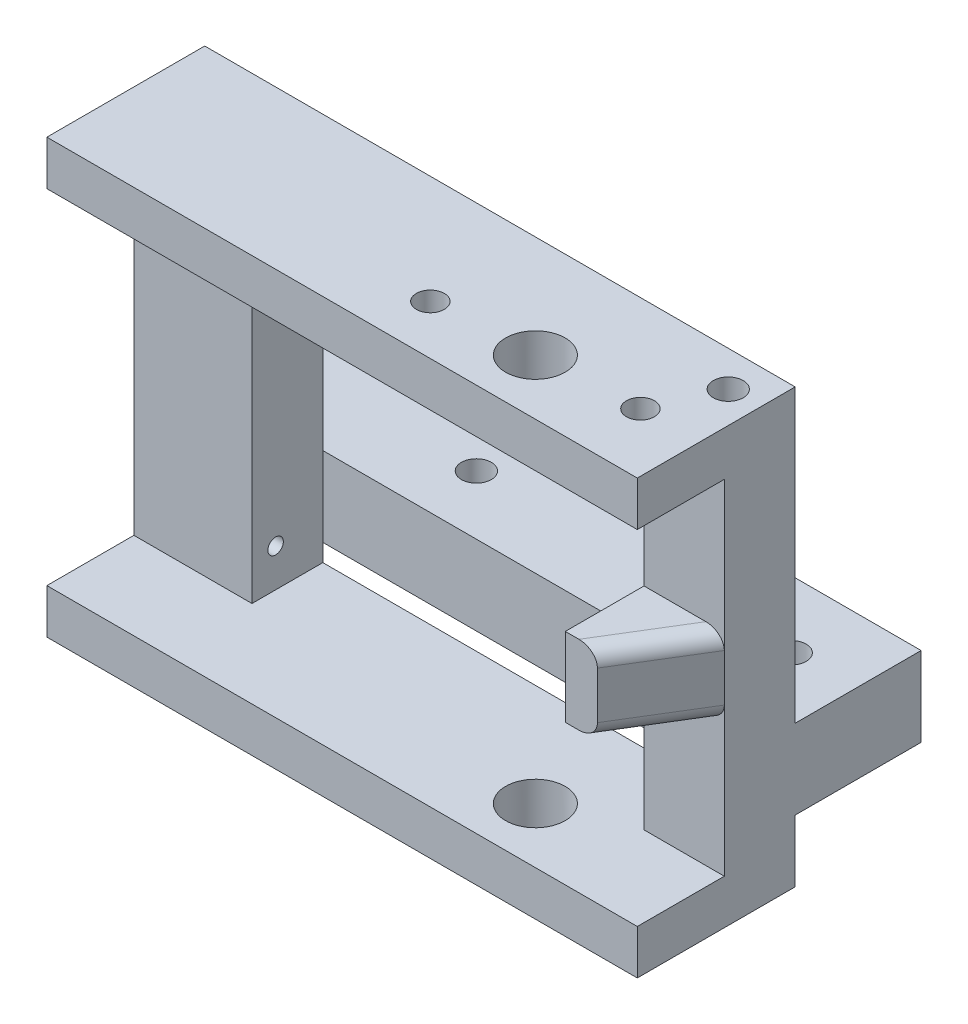
SolidWorks part; units mm, degrees
ref_plane "Front Plane" through (0, 0, 0) normal (0, 0, 1) x (1, 0, 0)
ref_plane "Top Plane" through (0, 0, 0) normal (0, 1, 0) x (1, 0, 0)
ref_plane "Right Plane" through (0, 0, 0) normal (1, 0, 0) x (0, 0, -1)
sketch "Sketch1" plane through (0, 0, 0) normal (0, 0, 1) x (1, 0, 0)
  line L1 (57.15, -34.925) -> (-57.15, -34.925)
  line L2 (57.15, -34.925) -> (57.15, 34.925)
  line L3 (57.15, 34.925) -> (-57.15, 34.925)
  line L4 (-57.15, -34.925) -> (-57.15, 34.925)
  line L5 (57.15, -34.925) -> (-57.15, 34.925) construction
  line L6 (57.15, 34.925) -> (-57.15, -34.925) construction
  point P0 (0, 0)
  dimension "D1" = 69.85
  dimension "D2" = 114.3
extrude "Boss-Extrude1" add sketch "Sketch1" along normal blind 57.15
sketch "Sketch2" plane through (0, 0, 57.15) normal (0, 0, 1) x (1, 0, 0)
  line L0 (-57.15, 34.925) -> (-57.15, -34.925) construction
  line L1 (57.15, -27.725) -> (-57.15, -27.725)
  line L2 (57.15, -27.725) -> (57.15, 27.725)
  line L3 (57.15, 27.725) -> (-57.15, 27.725)
  line L4 (-57.15, -27.725) -> (-57.15, 27.725)
  line L5 (57.15, -27.725) -> (-57.15, 27.725) construction
  line L6 (57.15, 27.725) -> (-57.15, -27.725) construction
  line L7 (57.15, 34.925) -> (-57.15, 34.925) construction
  point P0 (0, 0)
  dimension "D1" = 7.2
extrude "Cut-Extrude2" cut sketch "Sketch2" against normal blind 25.4
sketch "Sketch3" plane through (0, 0, 0) normal (0, 0, -1) x (-1, 0, 0)
  line L0 (-57.15, -34.925) -> (-57.15, 34.925) construction
  line L1 (57.15, 34.925) -> (-57.15, 34.925)
  line L2 (57.15, 34.925) -> (57.15, -12.065)
  line L3 (57.15, -12.065) -> (-57.15, -12.065)
  line L4 (-57.15, 34.925) -> (-57.15, -12.065)
  dimension "D1" = 46.99
extrude "Cut-Extrude3" cut sketch "Sketch3" against normal blind 20.32
sketch "Sketch5" plane through (0, -34.925, 0) normal (0, -1, 0) x (1, 0, 0)
  line L0 (-3.81, 10.79) -> (46.99, 10.79) construction
  line L1 (57.15, 20.32) -> (-57.15, 20.32) construction
  line L2 (57.15, 57.15) -> (57.15, 0) construction
  circle A0 centre (-3.81, 10.79) radius 2.415
  circle A1 centre (46.99, 10.79) radius 2.415
  dimension "D3" = 4.83
  dimension "D4" = 10.16
  dimension "D1" = 9.53
  dimension "D2" = 50.8
sketch "Sketch7" plane through (0, -34.925, 0) normal (0, -1, 0) x (1, 0, 0)
  line L0 (57.15, 57.15) -> (57.15, 0) construction
  line L2 (-57.15, 31.75) -> (57.15, 31.75) construction
  circle A0 centre (31.75, 36.83) radius 4.8
  dimension "D1" = 9.6
  dimension "D2" = 25.4
  dimension "D3" = 5.08
extrude "Cut-Extrude6" cut sketch "Sketch7" against normal up to surface (69.85 mm away) up to face at (0, 34.925, 38.735)
sketch "Sketch8" plane through (0, 34.925, 0) normal (0, 1, 0) x (1, 0, 0)
  line L0 (15.7798, -37.8068) -> (47.7202, -35.8532) construction
  line L1 (57.15, -31.75) -> (-57.15, -31.75) construction
  circle A0 centre (31.75, -36.83) radius 16 construction
  circle A1 centre (15.7798, -37.8068) radius 2.25
  circle A2 centre (47.7202, -35.8532) radius 2.25
  dimension "D1" = 32
  dimension "D2" = 4.5
  dimension "D3" = 3.5
sketch "Sketch9" plane through (0, 0, 31.75) normal (0, 0, 1) x (1, 0, 0)
  line L0 (57.15, 34.925) -> (-57.15, 34.925) construction
  line L5 (57.15, 27.725) -> (-57.15, 27.725) construction
  line L6 (-19.05, 27.725) -> (44.196, 27.725)
  line L7 (-19.05, 27.725) -> (-19.05, -27.725)
  line L8 (-19.05, -27.725) -> (44.196, -27.725)
  line L9 (44.196, 27.725) -> (44.196, -27.725)
  line L10 (-57.15, -27.725) -> (57.15, -27.725) construction
  line L11 (-57.15, 27.725) -> (-57.15, -27.725) construction
  line L12 (57.15, -27.725) -> (57.15, 27.725) construction
  line L13 (-57.15, -34.925) -> (-38.1, -34.925)
  line L14 (-57.15, -34.925) -> (-57.15, 34.925)
  line L15 (-57.15, 34.925) -> (-38.1, 34.925)
  line L16 (-38.1, -34.925) -> (-38.1, 34.925)
  line L17 (-57.15, -34.925) -> (-38.1, 34.925) construction
  line L18 (-57.15, 34.925) -> (-38.1, -34.925) construction
  line L19 (-57.15, -34.925) -> (57.15, -34.925) construction
  point P5 (-47.625, 0)
  dimension "D1" = 12.954
  dimension "25in" = 38.1
  dimension "D2" = 19.05
extrude "Cut-Extrude7" cut sketch "Sketch9" against normal through all both and the other way through all
extrude "Cut-Extrude8" cut sketch "Sketch8" against normal up to next
sketch "Sketch10" [suppressed] plane through (0, 0, 29.21) normal (0, 0, 1) x (1, 0, 0)
  line L1 (-30.607, -1.778) -> (-30.607, -6.604) construction
  circle A0 centre (-33.2489, -4.191) radius 2.286
  point P5 (-30.607, -4.191)
  dimension "D1" = 4.572
sketch "Sketch11" [suppressed] plane through (0, 0, 20.32) normal (0, 0, -1) x (-1, 0, 0)
  circle A0 centre (33.2489, -4.191) radius 2.286
  dimension "D1" = 4.572
extrude "Cut-Extrude9" [suppressed] cut sketch "Sketch11" against normal blind 3.81
sketch "Sketch12" plane through (-19.05, 0, 0) normal (1, 0, 0) x (0, 0, -1)
  line L0 (-31.75, -27.725) -> (-31.75, 27.725) construction
  line L1 (-27.94, -21.59) -> (-27.94, 21.59) construction
  line L2 (-20.32, 27.725) -> (-20.32, -12.065) construction
  circle A0 centre (-27.94, -21.59) radius 1.25
  circle A1 centre (-27.94, 21.59) radius 1.25
  point P0 (-31.75, 0)
  point P8 (-27.94, 0)
  dimension "D1" = 2.5
  dimension "D2" = 7.62
  dimension "D3" = 43.18
extrude "Cut-Extrude10" cut sketch "Sketch12" against normal up to surface (19.05 mm away) up to face at (-38.1, -2.413, 33.274)
sketch "Sketch13" plane through (0, 34.925, 0) normal (0, 1, 0) x (1, 0, 0)
  line L0 (-38.1, -45.7884) -> (57.15, -45.7884)
  line L2 (57.15, -57.15) -> (-38.1, -57.15) construction
  line L3 (47.7202, -35.8532) -> (15.7798, -37.8068) construction
  line L4 (-38.1, -45.7884) -> (-38.1, -57.15)
  line L5 (-38.1, -57.15) -> (57.15, -57.15)
  line L6 (-38.1, -20.32) -> (-38.1, -57.15) construction
  line L7 (57.15, -57.15) -> (57.15, -20.32) construction
  line L8 (57.15, -45.7884) -> (57.15, -57.15)
extrude "Cut-Extrude12" cut sketch "Sketch13" against normal through all
sketch "Sketch14" plane through (44.196, 0, 0) normal (-1, 0, 0) x (0, 0, 1)
  line L0 (0, -27.725) -> (31.75, -27.725) construction
  line L1 (20.32, -12.065) -> (0, -12.065)
  line L2 (20.32, -12.065) -> (20.32, -27.725)
  line L3 (20.32, -27.725) -> (0, -27.725)
  line L4 (0, -12.065) -> (0, -27.725)
extrude "Boss-Extrude2" add sketch "Sketch14" along normal up to next
sketch "Sketch16" plane through (0, 0, 31.75) normal (0, 0, 1) x (1, 0, 0)
  line L0 (44.196, -27.725) -> (44.196, 27.725) construction
  line L1 (57.15, -6.35) -> (44.196, -6.35)
  line L2 (57.15, -6.35) -> (57.15, 6.35)
  line L3 (57.15, 6.35) -> (44.196, 6.35)
  line L4 (44.196, -6.35) -> (44.196, 6.35)
  line L5 (57.15, -6.35) -> (44.196, 6.35) construction
  line L6 (57.15, 6.35) -> (44.196, -6.35) construction
  line L7 (57.15, 6.35) -> (57.15, -6.35) construction
  line L9 (57.15, -27.725) -> (57.15, 27.725) construction
  point P0 (50.673, 0)
  point P7 (57.15, 0)
  dimension "D1" = 12.7
extrude "Boss-Extrude3" add sketch "Sketch16" along normal blind 12.7
sketch "Sketch17" plane through (0, 6.35, 0) normal (0, 1, 0) x (1, 0, 0)
  line L0 (49.375, -44.45) -> (57.15, -31.75)
  line L1 (57.15, -44.45) -> (57.15, -31.75) construction
  line L2 (57.15, -31.75) -> (44.196, -31.75) construction
  line L3 (57.15, -31.75) -> (57.15, -44.45)
  line L4 (57.15, -44.45) -> (49.375, -44.45)
  line L5 (57.15, -44.45) -> (44.196, -44.45) construction
extrude "Cut-Extrude14" cut sketch "Sketch17" against normal blind 12.7
fillet "Fillet4" radius 2.54 2 edges at (53.2625, -6.35, 38.1) (53.2625, 6.35, 38.1)
sketch "Sketch18" plane through (-38.1, 0, 0) normal (-1, 0, 0) x (0, 0, 1)
  line L0 (0, -34.925) -> (45.7884, -34.925) construction
  line L1 (20.32, -35.0627) -> (20.32, -24.9001)
  line L2 (20.32, -24.9001) -> (0, -24.9001)
  line L3 (0, -34.925) -> (0, -12.065) construction
  line L4 (0, -24.9001) -> (0, -34.925)
  line L5 (20.32, -34.925) -> (0, -34.925)
  point P0 (20.32, -34.925)
  point P1 (7.9478, 3.6724)
  line M3 (0, -34.925) -> (45.7884, -34.925)
  line M12 (0, -12.065) -> (0, -34.925)
sketch "Sketch19" plane through (-38.1, 0, 0) normal (-1, 0, 0) x (0, 0, 1)
  line L0 (20.32, -34.925) -> (0, -34.925)
sketch "Sketch20" plane through (-38.1, 0, 0) normal (-1, 0, 0) x (0, 0, 1)
  line L0 (0, -34.925) -> (45.7884, -34.925) construction
  line L1 (20.066, -34.925) -> (20.066, -24.765)
  line L2 (20.066, -24.765) -> (0, -24.765)
  line L3 (0, -34.925) -> (0, -12.065) construction
  line L4 (0, -24.765) -> (0, -34.925)
  line L5 (20.066, -34.925) -> (-0.1509, -34.925)
  point P0 (20.32, -34.925)
  dimension "D1" = 10.16
  dimension "D2" = 20.066
extrude "Cut-Extrude20" cut sketch "Sketch5" against normal through all contours A0 | A1
sketch "Sketch21" plane through (-38.1, 0, 0) normal (-1, 0, 0) x (0, 0, 1)
sketch "Sketch22" plane through (-38.1, 0, 0) normal (-1, 0, 0) x (0, 0, 1)
extrude "Cut-Extrude21" cut sketch "Sketch18" against normal through all contours L1 L2 M12 M3 region at (-38.1, -29.9125, 10.16)
sketch "Sketch23" plane through (0, -34.925, 0) normal (0, -1, 0) x (1, 0, 0)
  line L0 (57.15, 20.32) -> (57.15, 31.75)
  line L1 (57.15, 45.7884) -> (57.15, 20.32) construction
  circle A0 centre (52.07, 26.035) radius 2.413
  point P7 (57.15, 26.035)
  dimension "D2" = 4.826
  dimension "D1" = 11.43
  dimension "D3" = 5.08
extrude "Cut-Extrude22" cut sketch "Sketch23" against normal through all contours A0
sketch "Sketch24" plane through (0, 34.925, 0) normal (0, 1, 0) x (1, 0, 0)
  line L0 (47.7202, -35.8532) -> (15.7798, -37.8068)
  point P0 (47.7202, -35.8532)
  point P1 (15.7798, -37.8068)
sketch3d "3DSketch2"
  line L1 (47.7202, 34.925, 35.8532) -> (15.7798, 34.925, 37.8068) construction
